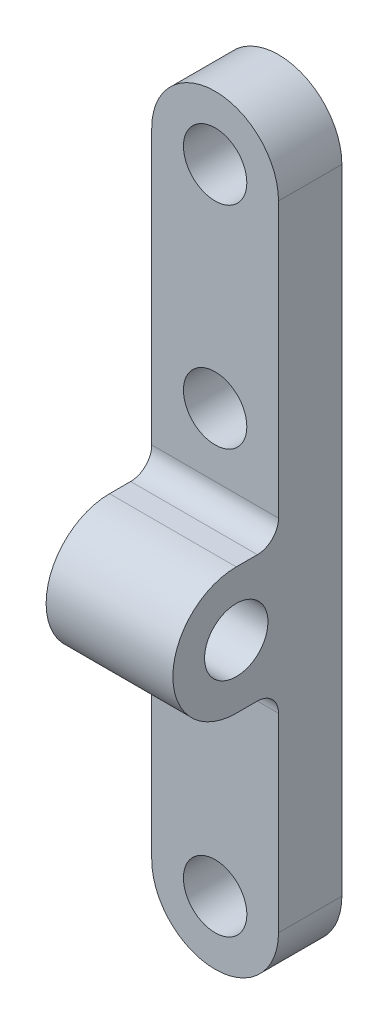
SolidWorks part; units mm, degrees
material "ABS"
ref_plane "正面" through (0, 0, 0) normal (0, 0, 1) x (1, 0, 0)
ref_plane "平面" through (0, 0, 0) normal (0, 1, 0) x (1, 0, 0)
ref_plane "右側面" through (0, 0, 0) normal (1, 0, 0) x (0, 0, -1)
sketch "ｽｹｯﾁ1" plane through (0, 0, 0) normal (0, 0, 1) x (1, 0, 0)
  line L0 (0, 0) -> (0, -30) construction
  line L1 (-3, 0) -> (-3, -30)
  line L2 (3, 0) -> (3, -30)
  line L3 (0, -15) -> (-3, -15) construction
  circle A0 centre (0, 0) radius 1.5
  arc A1 (3, 0) -> (-3, 0) centre (0, 0) ccw
  circle A2 centre (0, -30) radius 1.5
  arc A3 (3, -30) -> (-3, -30) centre (0, -30) cw
  arc A4 (0, -3) -> (3, 0) centre (0, 0) ccw construction
  arc A5 (-3, 0) -> (0, -3) centre (0, 0) ccw construction
  arc A6 (-3, -30) -> (0, -27) centre (0, -30) cw construction
  arc A7 (0, -27) -> (3, -30) centre (0, -30) cw construction
  dimension "D1" = 3
  dimension "D2" = 6
  dimension "D3" = 6
  dimension "D4" = 30
extrude "ﾎﾞｽ - 押し出し1" add sketch "ｽｹｯﾁ1" along normal blind 3
sketch "ｽｹｯﾁ2" plane through (3, 0, 0) normal (1, 0, 0) x (0, 0, -1)
  line L1 (0, -14) -> (-5, -14)
  line L3 (-5, -20) -> (0, -20)
  line L4 (0, -20) -> (0, -14)
  line L5 (-3, -30) -> (0, -30) construction
  line L6 (0, -30) -> (0, 0) construction
  line L7 (-3, -30) -> (-3, 0) construction
  circle A0 centre (-5, -17) radius 1.5
  arc A1 (-5, -20) -> (-5, -14) centre (-5, -17) cw
  dimension "D1" = 3
  dimension "D2" = 3
  dimension "D3" = 13
  dimension "D4" = 2
extrude "ﾎﾞｽ - 押し出し4" add sketch "ｽｹｯﾁ2" against normal up to surface (6 mm away) up to face at (-3, -15, 1.5)
fillet "ﾌｨﾚｯﾄ1" radius 1 2 edges at (0, -20, 3) (0, -14, 3)
sketch "ｽｹｯﾁ3" plane through (0, 0, 0) normal (0, 0, -1) x (-1, 0, 0)
  line L0 (0, 0) -> (0, -10) construction
  circle A0 centre (0, -10) radius 1.5
  dimension "D1" = 3
  dimension "D2" = 10
extrude "ｶｯﾄ - 押し出し1" cut sketch "ｽｹｯﾁ3" against normal blind 10
